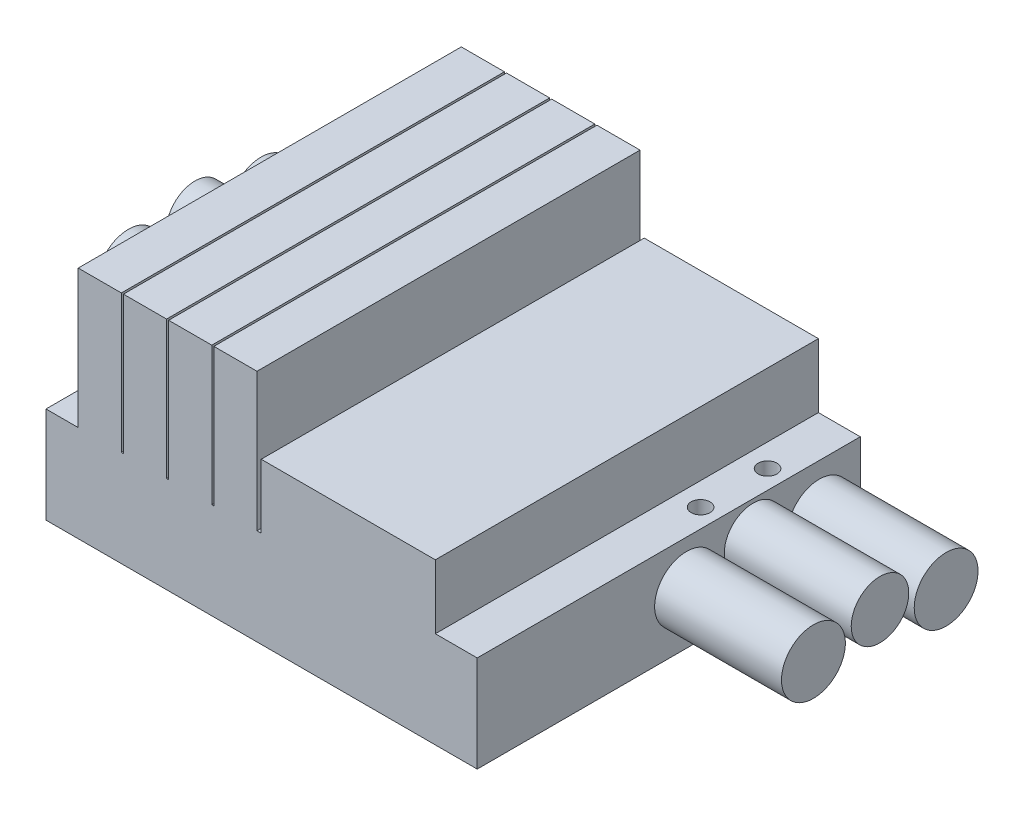
SolidWorks part; units mm, degrees
ref_plane "Front Plane" through (0, 0, 0) normal (0, 0, 1) x (1, 0, 0)
ref_plane "Top Plane" through (0, 0, 0) normal (0, 1, 0) x (1, 0, 0)
ref_plane "Right Plane" through (0, 0, 0) normal (1, 0, 0) x (0, 0, -1)
sketch "Sketch1" plane through (0, 0, 0) normal (0, 1, 0) x (1, 0, 0)
  line L0 (-47, 45.75) -> (-47, 30.25) construction
  line L1 (-51.5, -45.75) -> (51.5, -45.75)
  line L2 (-51.5, -45.75) -> (-51.5, 45.75)
  line L3 (-51.5, 45.75) -> (51.5, 45.75)
  line L4 (51.5, -45.75) -> (51.5, 45.75)
  line L5 (-51.5, -45.75) -> (51.5, 45.75) construction
  line L6 (-51.5, 45.75) -> (51.5, -45.75) construction
  line L7 (-47, 45.75) -> (-47, 14.25) construction
  line L8 (-47, 30.25) -> (-47, 28.1) construction
  line L9 (-47, 14.25) -> (-47, 12.1) construction
  line L10 (-47, 28.1) -> (-51.5, 28.1) construction
  line L11 (-47, 12.1) -> (-51.5, 12.1) construction
  line L12 (-47, 12.1) -> (47, 12.1) construction
  line L13 (-47, 28.1) -> (47, 28.1) construction
  circle A0 centre (-47, 28.1) radius 2.15
  circle A1 centre (-47, 12.1) radius 2.15
  circle A2 centre (47, 28.1) radius 2.25
  circle A3 centre (47, 12.1) radius 2.25
  point P0 (0, 0)
  point P20 (0, 0)
  dimension "D9" = 4.5
  dimension "D10" = 4.5
  dimension "D1" = 91.5
  dimension "D2" = 103
  dimension "D3" = 15.5
  dimension "D4" = 31.5
  dimension "D5" = 2.15
  dimension "D6" = 2.15
  dimension "D7" = 4.5
  dimension "D8" = 4.5
  dimension "D11" = 94
  dimension "D12" = 94
extrude "Boss-Extrude1" add sketch "Sketch1" along normal blind 23 contours A3 | A2 | L2 L1 L4 L3 | A0 | A1
sketch "Sketch2" plane through (-51.5, 0, 0) normal (-1, 0, 0) x (0, 0, 1)
  line L0 (-45.75, 11.5) -> (-35.95, 11.5) construction
  line L1 (-45.75, 15.2) -> (-20.15, 15.2) construction
  line L2 (-35.95, 11.5) -> (-35.95, 0) construction
  line L4 (-45.75, 23) -> (-45.75, 0) construction
  line L5 (-20.15, 15.2) -> (-20.15, 0) construction
  line L6 (-45.75, 12.4) -> (-4.25, 12.4) construction
  line L7 (-4.25, 12.4) -> (-4.25, 0) construction
  circle A0 centre (-35.95, 11.5) radius 7.625
  circle A1 centre (-20.15, 15.2) radius 6.875
  circle A2 centre (-4.25, 12.4) radius 7.625
  dimension "D3" = 15.25
  dimension "D6" = 13.75
  dimension "D9" = 15.25
  dimension "D1" = 9.8
  dimension "D2" = 11.5
  dimension "D4" = 25.6
  dimension "D5" = 15.2
  dimension "D7" = 12.4
  dimension "D8" = 41.5
extrude "Boss-Extrude2" add sketch "Sketch2" along normal blind 30.31 from surface contours A1 | A0 | A2 starting at face at (-51.5, 11.5, 0)
sketch "Sketch4" plane through (0, 0, -45.75) normal (0, 0, -1) x (-1, 0, 0)
  line L0 (-51.5, 5.4) -> (5.8, 5.4) construction
  line L1 (-51.5, 19.125) -> (-51.5, 3.875) construction
  line L2 (5.8, 5.4) -> (5.8, 23) construction
  line L4 (-51.5, 17.6) -> (0.8, 17.6) construction
  line L5 (-51.5, 23) -> (-51.5, 0) construction
  line L6 (0.8, 17.6) -> (0.8, 23) construction
  circle A0 centre (5.8, 5.4) radius 4.9
  circle A1 centre (0.8, 17.6) radius 4.9
  circle A2 centre (11.3, 17.6) radius 4.9
  circle A3 centre (16.3, 5.4) radius 4.9
  circle A4 centre (21.8, 17.6) radius 4.9
  circle A5 centre (26.8, 5.4) radius 4.9
  circle A6 centre (32.3, 17.6) radius 4.9
  circle A7 centre (37.3, 5.4) radius 4.9
  point P15 (0, 0)
  dimension "D5" = 9.8
  dimension "D6" = 9.8
  dimension "D1" = 57.3
  dimension "D2" = 17.6
  dimension "D3" = 52.3
  dimension "D4" = 5.4
  dimension "D7" = 4
extrude "Boss-Extrude3" add sketch "Sketch4" along normal blind 14.15
extrude "Boss-Extrude4" add sketch "Sketch2<7>" against normal blind 30.31 from surface starting at face at (51.5, 11.5, 0)
sketch "Sketch2<7>" plane through (-51.5, 0, 0) normal (-1, 0, 0) x (0, 0, 1) same geometry as "Sketch2"
sketch "Sketch6" plane through (0, 23, 0) normal (0, 1, 0) x (1, 0, 0)
  line L0 (51.5, 41.6244) -> (41.5, 41.6244) construction
  line L1 (51.5, -45.75) -> (51.5, 45.75) construction
  line L2 (51.5, 0) -> (-51.5, 0) construction
  line L3 (-51.5, -45.75) -> (-51.5, 45.75) construction
  line L9 (41.5, 41.6244) -> (41.5, -45.75) construction
  line L10 (-51.5, -45.75) -> (51.5, -45.75) construction
  line L11 (-51.5, 45.75) -> (51.5, 45.75) construction
  line L12 (41.5, -45.75) -> (-0.1, -45.75)
  line L13 (41.5, -45.75) -> (41.5, 45.75)
  line L14 (41.5, 45.75) -> (-0.1, 45.75)
  line L15 (-0.1, -45.75) -> (-0.1, 45.75)
  line L16 (-0.1, 9.576) -> (-1.1, 9.576) construction
  line L17 (-1.1, 9.576) -> (-1.1, 45.75) construction
  line L18 (-11.9, 45.75) -> (-11.9, -45.75)
  line L19 (-1.1, 45.75) -> (-11.4, 45.75)
  line L20 (-1.1, 45.75) -> (-1.1, -45.75)
  line L21 (-1.1, -45.75) -> (-11.4, -45.75)
  line L22 (-11.4, 45.75) -> (-11.4, -45.75)
  line L23 (-11.9, 45.75) -> (-22.2, 45.75)
  line L24 (-22.2, 45.75) -> (-22.2, -45.75)
  line L25 (-11.9, -45.75) -> (-22.2, -45.75)
  line L26 (-22.7, 45.75) -> (-22.7, -45.75)
  line L27 (-22.7, 45.75) -> (-33, 45.75)
  line L28 (-33, 45.75) -> (-33, -45.75)
  line L29 (-22.7, -45.75) -> (-33, -45.75)
  line L30 (-33.5, 45.75) -> (-33.5, -45.75)
  line L31 (-33.5, 45.75) -> (-43.8, 45.75)
  line L32 (-43.8, 45.75) -> (-43.8, -45.75)
  line L33 (-33.5, -45.75) -> (-43.8, -45.75)
  dimension "D1" = 10
  dimension "D2" = 41.6
  dimension "D3" = 1
  dimension "D4" = 10.3
  dimension "D5" = 4
extrude "Boss-Extrude5" add sketch "Sketch6" along normal blind 15.3 contours L13 L12 L15 L14
extrude "Boss-Extrude7" add sketch "Sketch6<5>" along normal blind 33 contours L20 L21 L22 L19 | L18 L25 L24 L23 | L26 L29 L28 L27 | L30 L33 L32 L31
sketch "Sketch6<5>" plane through (0, 23, 0) normal (0, 1, 0) x (1, 0, 0) same geometry as "Sketch6"
